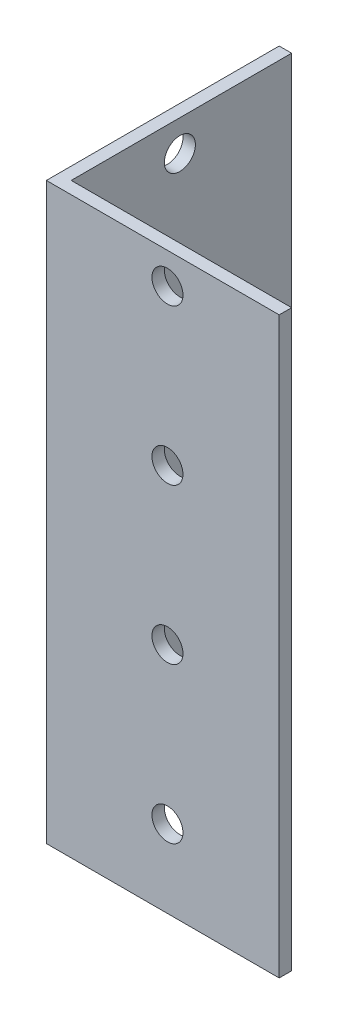
SolidWorks part; units mm, degrees
ref_plane "Спереди" through (0, 0, 0) normal (0, 0, 1) x (1, 0, 0)
ref_plane "Сверху" through (0, 0, 0) normal (0, 1, 0) x (1, 0, 0)
ref_plane "Справа" through (0, 0, 0) normal (1, 0, 0) x (0, 0, -1)
sketch "Эскиз1" plane through (0, 0, 0) normal (0, 1, 0) x (1, 0, 0)
  line L0 (0, 0) -> (75, 0)
  line L1 (0, 0) -> (0, 75)
extrude "Вытянуть-Тонкостенный1" add sketch "Эскиз1" along normal blind 185 thin thin type one direction wall 4
sketch "Эскиз2" plane through (0, 0, 0) normal (0, 0, 1) x (1, 0, 0)
  circle A0 centre (39, 175) radius 5
  circle A1 centre (39, 125) radius 5
  circle A2 centre (39, 75) radius 5
  circle A3 centre (39, 25) radius 5
  dimension "D1" = 4
extrude "Вырез-Вытянуть1" cut sketch "Эскиз2" against normal blind 10
sketch "Эскиз3" plane through (0, 0, 0) normal (-1, 0, 0) x (0, 0, 1)
  circle A0 centre (-39, 175) radius 5
  circle A1 centre (-39, 125) radius 5
  circle A2 centre (-39, 75) radius 5
  circle A3 centre (-39, 25) radius 5
  dimension "D1" = 4
extrude "Вырез-Вытянуть2" cut sketch "Эскиз3" against normal blind 10
